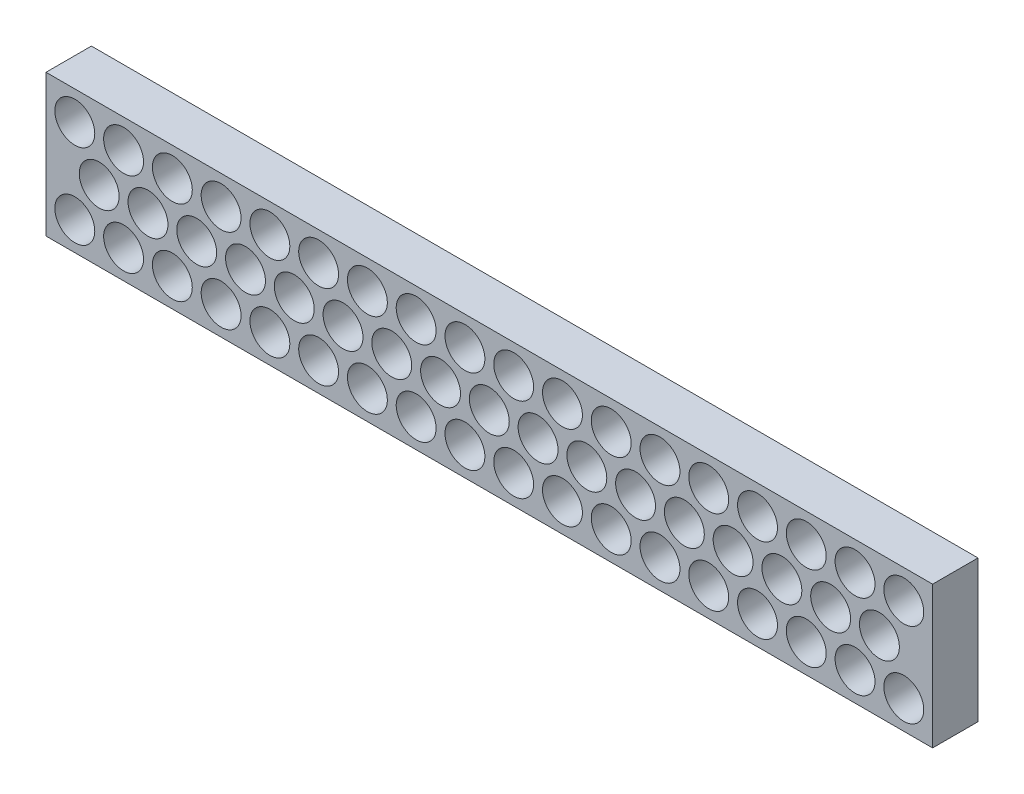
SolidWorks part; units mm, degrees
ref_plane "Front Plane" through (0, 0, 0) normal (0, 0, 1) x (1, 0, 0)
ref_plane "Top Plane" through (0, 0, 0) normal (0, 1, 0) x (1, 0, 0)
ref_plane "Right Plane" through (0, 0, 0) normal (1, 0, 0) x (0, 0, -1)
sketch "Sketch1" plane through (0, 0, 0) normal (0, 0, 1) x (1, 0, 0)
  line L0 (0, 0) -> (17.4625, 0) construction
  line L1 (17.4625, 0) -> (17.4625, 30.2463) construction
  line L2 (17.4625, 30.2463) -> (31.75, 30.2463) construction
  line L3 (38.1, -50.7162) -> (-596.9, -50.7162)
  line L4 (38.1, -50.7162) -> (38.1, 50.8838)
  line L5 (38.1, 50.8838) -> (-596.9, 50.8838)
  line L6 (-596.9, -50.7162) -> (-596.9, 50.8838)
  line L7 (17.4625, 30.2463) -> (17.4625, 44.5338) construction
  circle A0 centre (0, 0) radius 14.2875
  circle A1 centre (17.4625, 30.2463) radius 14.2875
  circle A2 centre (17.4625, -30.2463) radius 14.2875
  dimension "D1" = 28.575
  dimension "D4" = 28.575
  dimension "D2" = 17.4625
  dimension "D3" = 30.2463
  dimension "D5" = 6.35
  dimension "D6" = 635
  dimension "D7" = 101.6
  dimension "D8" = 6.35
extrude "Boss-Extrude1" add sketch "Sketch1" against normal blind 32.512 contours L5 L6 L3 L4
extrude "Cut-Extrude2" cut sketch "Sketch1<3>" against normal through all both and the other way through all contours A0 | A1 | A2 region at (0, 0, 0) region at (17.4625, 30.2463, 0) region at (17.4625, -30.2463, 0)
sketch "Sketch1<3>" plane through (0, 0, 0) normal (0, 0, 1) x (1, 0, 0) same geometry as "Sketch1"
pattern_linear "LPattern1" count 17 spacing 34.925 along (-1, 0, 0) of "Cut-Extrude2"
sketch "Sketch3" plane through (0, 0, 0) normal (0, 0, 1) x (1, 0, 0)
  line L0 (-541.3375, 30.2463) -> (-576.2625, 30.2463) construction
  line L1 (-541.3375, -30.2463) -> (-576.2625, -30.2463) construction
  circle A0 centre (-576.2625, 30.2463) radius 14.2875
  circle A1 centre (-576.2625, -30.2463) radius 14.2875
  dimension "D1" = 28.575
  dimension "D4" = 28.575
  dimension "D2" = 34.925
  dimension "D3" = 34.925
extrude "Cut-Extrude3" cut sketch "Sketch3" against normal through all both contours A0 | A1 region at (-576.2625, 30.2463, 0) region at (-576.2625, -30.2463, 0)
